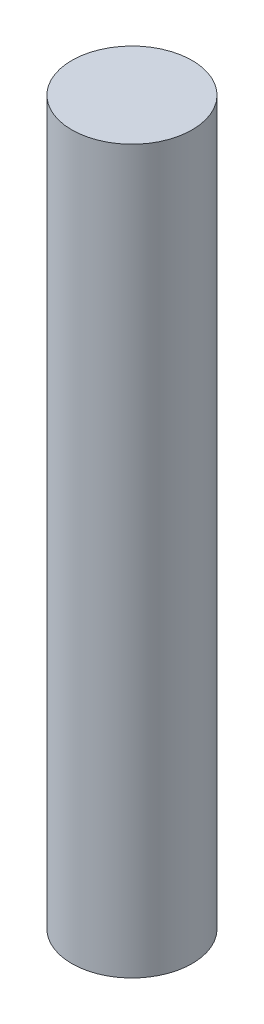
SolidWorks part; units mm, degrees
ref_plane "Front Plane" through (0, 0, 0) normal (0, 0, 1) x (1, 0, 0)
ref_plane "Top Plane" through (0, 0, 0) normal (0, 1, 0) x (1, 0, 0)
ref_plane "Right Plane" through (0, 0, 0) normal (1, 0, 0) x (0, 0, -1)
sketch3d "3DSketch1" plane through (0, 0, 0) normal (0, 0, 1) x (1, 0, 0)
  dimension "D1" = 69
sketch "Sketch1" plane through (0, -69, 0) normal (0, 1, 0) x (1, 0, 0)
  circle A0 centre (0, 0) radius 25
  dimension "D1" = 50
extrude "Boss-Extrude1" add sketch "Sketch1" against normal blind 300
